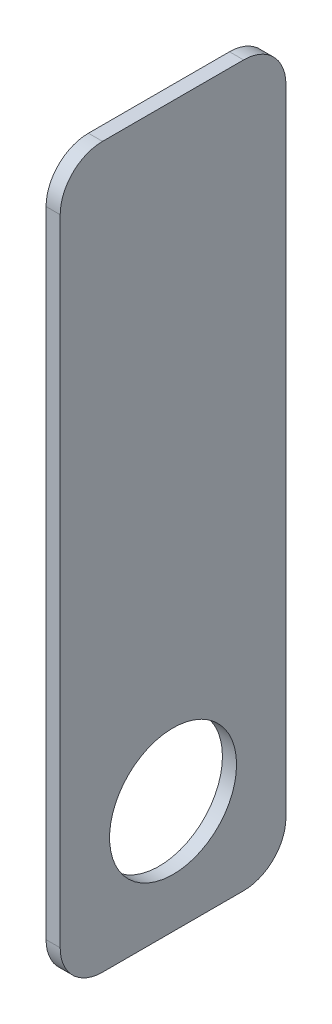
SolidWorks part; units mm, degrees
material "6063-O"
ref_plane "Front" through (0, 0, 0) normal (0, 0, 1) x (1, 0, 0)
ref_plane "Top" through (0, 0, 0) normal (0, 1, 0) x (1, 0, 0)
ref_plane "Right" through (0, 0, 0) normal (1, 0, 0) x (0, 0, -1)
sketch "Sketch1" plane through (0, 0, 0) normal (1, 0, 0) x (0, 0, -1)
  line L0 (0, 80.9625) -> (0, -80.9625) construction
  line L1 (-25.4, 80.9625) -> (25.4, 80.9625)
  line L2 (-25.4, 80.9625) -> (-25.4, -80.9625)
  line L3 (-25.4, -80.9625) -> (25.4, -80.9625)
  line L4 (25.4, 80.9625) -> (25.4, -80.9625)
  circle A0 centre (0, -55.5625) radius 14.2875
  point P4 (0, 0)
  dimension "D3" = 28.575
  dimension "D1" = 50.8
  dimension "D2" = 136.525
  dimension "D4" = 25.4
extrude "Boss-Extrude1" add sketch "Sketch1" along normal blind 3.175
fillet "Fillet1" radius 9.525 4 edges at (1.5875, -80.9625, -25.4) (1.5875, -80.9625, 25.4) (1.5875, 80.9625, -25.4) (1.5875, 80.9625, 25.4)
